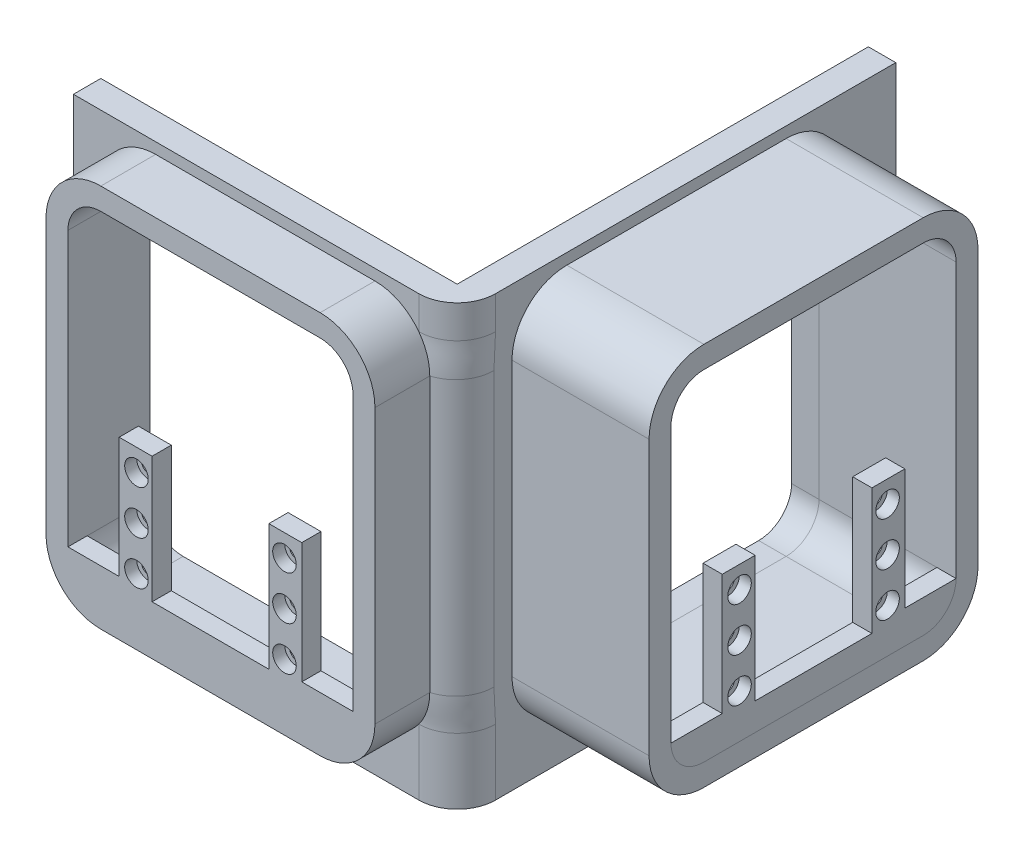
SolidWorks part; units mm, degrees
ref_plane "Front Plane" through (0, 0, 0) normal (0, 0, 1) x (1, 0, 0)
ref_plane "Top Plane" through (0, 0, 0) normal (0, 1, 0) x (1, 0, 0)
ref_plane "Right Plane" through (0, 0, 0) normal (1, 0, 0) x (0, 0, -1)
sketch "Sketch1" plane through (0, 0, 0) normal (0, 0, 1) x (1, 0, 0)
  line L1 (-20, -35) -> (20, -35)
  line L2 (-30, -25) -> (-30, 25)
  line L3 (-20, 35) -> (20, 35)
  line L4 (30, -25) -> (30, 25)
  line L5 (-30, -35) -> (30, 35) construction
  line L6 (-30, 35) -> (30, -35) construction
  arc A1 (20, 35) -> (30, 25) centre (20, 25) cw
  arc A2 (20, -35) -> (30, -25) centre (20, -25) ccw
  arc A3 (-20, -35) -> (-30, -25) centre (-20, -25) cw
  arc A4 (-30, 25) -> (-20, 35) centre (-20, 25) cw
  point P0 (0, 0)
  dimension "D1" = 60
  dimension "D3" = 10
  dimension "D2" = 70
extrude "Boss-Extrude1" add sketch "Sketch1" against normal blind 10
ref_plane "Plane1" through (60, 0, 0) normal (1, 0, 0) x (0, 0, -1)
ref_plane "Plane2" through (60, 0, 0) normal (1, 0, 0) x (0, 0, -1)
sketch "Sketch10" plane through (0, 0, -10) normal (0, 0, -1) x (-1, 0, 0)
  line L0 (0, -3) -> (0, 0) construction
  line L1 (-35, -43) -> (35, -43)
  line L2 (-35, -43) -> (-35, 37)
  line L3 (-35, 37) -> (35, 37)
  line L4 (35, -43) -> (35, 37)
  line L5 (-35, -43) -> (35, 37) construction
  line L6 (-35, 37) -> (35, -43) construction
  point P0 (0, -3)
  dimension "D3" = 3
  dimension "D1" = 80
  dimension "D2" = 70
extrude "Boss-Extrude6" add sketch "Sketch10" along normal blind 80
sketch "Sketch2" plane through (60, 0, 0) normal (1, 0, 0) x (0, 0, -1)
  line L2 (0, 0) -> (146.6861, 0) construction
  line L3 (50, 0) -> (50, 30) construction
  line L5 (10, 37) -> (10, -43) construction
  line L6 (90, 37) -> (90, -43) construction
  line L7 (30, -35) -> (70, -35)
  line L8 (20, -25) -> (20, 25)
  line L9 (30, 35) -> (70, 35)
  line L10 (80, -25) -> (80, 25)
  line L11 (20, -35) -> (80, 35) construction
  line L12 (20, 35) -> (80, -35) construction
  arc A1 (30, -35) -> (20, -25) centre (30, -25) cw
  arc A2 (70, -35) -> (80, -25) centre (70, -25) ccw
  arc A3 (70, 35) -> (80, 25) centre (70, 25) cw
  arc A4 (20, 25) -> (30, 35) centre (30, 25) cw
  dimension "D1" = 60
  dimension "D3" = 10
  dimension "D2" = 70
extrude "Boss-Extrude2" add sketch "Sketch2" against normal up to surface (25 mm away) separate body up to face at (35, -3, -50)
sketch "Sketch11" plane through (0, 37, 0) normal (0, 1, 0) x (1, 0, 0)
  line L1 (-35, 90) -> (30, 90)
  line L2 (-35, 90) -> (-35, 15)
  line L3 (-35, 15) -> (30, 15)
  line L4 (30, 90) -> (30, 15)
  dimension "D1" = 75
  dimension "D2" = 65
extrude "Cut-Extrude5" cut sketch "Sketch11" against normal through all
sketch "Sketch4" plane through (35, 0, 0) normal (-1, 0, 0) x (0, 0, 1)
  line L8 (-70, -31) -> (-30, -31)
  line L9 (-76, 25) -> (-76, -25)
  line L10 (-30, 31) -> (-70, 31)
  line L11 (-24, -25) -> (-24, 25)
  line L12 (-70, -31) -> (-30, -31)
  line L13 (-76, 25) -> (-76, -25)
  line L14 (-30, 31) -> (-70, 31)
  line L15 (-24, -25) -> (-24, 25)
  arc A10 (-76, -25) -> (-70, -31) centre (-70, -25) ccw
  arc A11 (-70, 31) -> (-76, 25) centre (-70, 25) ccw
  arc A12 (-24, 25) -> (-30, 31) centre (-30, 25) ccw
  arc A13 (-30, -31) -> (-24, -25) centre (-30, -25) ccw
  arc A14 (-76, -25) -> (-70, -31) centre (-70, -25) ccw
  arc A15 (-70, 31) -> (-76, 25) centre (-70, 25) ccw
  arc A16 (-24, 25) -> (-30, 31) centre (-30, 25) ccw
  arc A17 (-30, -31) -> (-24, -25) centre (-30, -25) ccw
  dimension "D1" = 4
extrude "Cut-Extrude2" cut sketch "Sketch4" against normal through all contours L12 A17 L15 A16 L14 A15 L13 A14 region at (35, 0, -50)
sketch "Sketch5" plane through (60, 0, 0) normal (1, 0, 0) x (0, 0, -1)
  line L0 (50, 0) -> (50, -31) construction
  line L1 (33.35, -3) -> (39.35, -3)
  line L2 (39.35, -3) -> (39.35, -26)
  line L3 (39.35, -26) -> (60.65, -26)
  line L4 (60.65, -26) -> (60.65, -3)
  line L5 (60.65, -3) -> (66.65, -3)
  line L6 (66.65, -3) -> (66.65, -25)
  line L8 (33.35, -3) -> (33.35, -25)
  line L10 (50, 0) -> (63.5, 0) construction
  line L11 (63.5, 0) -> (63.5, -7) construction
  line L12 (63.5, -7) -> (63.5, -15) construction
  line L13 (63.5, -15) -> (63.5, -23) construction
  line L14 (70, -31) -> (30, -31) construction
  line L15 (30, -31) -> (70, -31)
  line L16 (33.35, -25) -> (24, -25)
  line L17 (66.65, -25) -> (76, -25)
  circle A0 centre (50, 0) radius 11 construction
  arc A1 (24, -25) -> (30, -31) centre (30, -25) ccw construction
  circle A2 centre (63.5, -7) radius 1.25
  arc A3 (24, -25) -> (30, -31) centre (30, -25) ccw
  circle A5 centre (63.5, -15) radius 1.25
  circle A6 centre (63.5, -23) radius 1.25
  circle A7 centre (36.5, -7) radius 1.25
  circle A8 centre (36.5, -15) radius 1.25
  circle A9 centre (36.5, -23) radius 1.25
  arc A10 (70, -31) -> (76, -25) centre (70, -25) ccw
  point P8 (50, -26)
  point P14 (50, -31)
  dimension "D1" = 22
  dimension "D6" = 2.5
  dimension "D3" = 21.3
  dimension "D4" = 13.5
  dimension "D5" = 7
  dimension "D7" = 8
  dimension "D8" = 8
  dimension "D9" = 6
  dimension "D10" = 5
  dimension "D12" = 3
extrude "Boss-Extrude3" add sketch "Sketch5" against normal blind 3.5
sketch "Sketch13" plane through (35, 0, 0) normal (1, 0, 0) x (0, 0, -1)
  line L4 (24, 25) -> (24, -25)
  line L5 (30, -31) -> (70, -31)
  line L6 (76, -25) -> (76, 25)
  line L7 (70, 31) -> (30, 31)
  line L8 (24, 25) -> (24, -25)
  line L9 (30, -31) -> (70, -31)
  line L10 (76, -25) -> (76, 25)
  line L11 (70, 31) -> (30, 31)
  arc A6 (30, 31) -> (24, 25) centre (30, 25) ccw
  arc A7 (24, -25) -> (30, -31) centre (30, -25) ccw
  arc A8 (70, -31) -> (76, -25) centre (70, -25) ccw
  arc A9 (76, 25) -> (70, 31) centre (70, 25) ccw
  arc A10 (30, 31) -> (24, 25) centre (30, 25) ccw
  arc A11 (24, -25) -> (30, -31) centre (30, -25) ccw
  arc A12 (70, -31) -> (76, -25) centre (70, -25) ccw
  arc A13 (76, 25) -> (70, 31) centre (70, 25) ccw
  dimension "D1" = 0
extrude "Cut-Extrude6" cut sketch "Sketch13" against normal up to surface (5 mm away) up to face at (30, -3, -52.5)
sketch "Sketch14" plane through (0, 0, 0) normal (0, 0, 1) x (1, 0, 0)
  line L8 (20, 31) -> (-20, 31)
  line L9 (26, -25) -> (26, 25)
  line L10 (-20, -31) -> (20, -31)
  line L11 (-26, 25) -> (-26, -25)
  line L12 (20, 31) -> (-20, 31)
  line L13 (26, -25) -> (26, 25)
  line L14 (-20, -31) -> (20, -31)
  line L15 (-26, 25) -> (-26, -25)
  arc A10 (26, 25) -> (20, 31) centre (20, 25) ccw
  arc A11 (20, -31) -> (26, -25) centre (20, -25) ccw
  arc A12 (-26, -25) -> (-20, -31) centre (-20, -25) ccw
  arc A13 (-20, 31) -> (-26, 25) centre (-20, 25) ccw
  arc A14 (26, 25) -> (20, 31) centre (20, 25) ccw
  arc A15 (20, -31) -> (26, -25) centre (20, -25) ccw
  arc A16 (-26, -25) -> (-20, -31) centre (-20, -25) ccw
  arc A17 (-20, 31) -> (-26, 25) centre (-20, 25) ccw
  dimension "D1" = 4
extrude "Cut-Extrude7" cut sketch "Sketch14" against normal up to surface (15 mm away) up to face at (-2.5, -3, -15)
sketch "Sketch15" plane through (0, 0, 0) normal (0, 0, 1) x (1, 0, 0)
  line L0 (0, 0) -> (0, -17.9719) construction
  line L1 (-16.65, -3) -> (-10.65, -3)
  line L2 (-10.65, -3) -> (-10.65, -26)
  line L3 (-10.65, -26) -> (10.65, -26)
  line L4 (10.65, -26) -> (10.65, -3)
  line L5 (10.65, -3) -> (16.65, -3)
  line L6 (16.65, -3) -> (16.65, -25)
  line L8 (-16.65, -3) -> (-16.65, -25)
  line L10 (0, 0) -> (13.5, 0) construction
  line L11 (13.5, 0) -> (13.5, -7) construction
  line L12 (13.5, -7) -> (13.5, -15) construction
  line L13 (13.5, -15) -> (13.5, -23) construction
  line L14 (-20, -31) -> (20, -31) construction
  line L15 (-20, -31) -> (20, -31)
  line L16 (26, -25) -> (16.65, -25)
  line L17 (-26, -25) -> (-16.65, -25)
  circle A0 centre (0, 0) radius 11 construction
  circle A1 centre (13.5, -7) radius 1.25
  circle A3 centre (13.5, -15) radius 1.25
  circle A4 centre (13.5, -23) radius 1.25
  circle A5 centre (-13.5, -7) radius 1.25
  circle A6 centre (-13.5, -15) radius 1.25
  circle A7 centre (-13.5, -23) radius 1.25
  arc A9 (-26, -25) -> (-20, -31) centre (-20, -25) ccw
  arc A10 (26, -25) -> (20, -31) centre (20, -25) cw
  point P5 (0, -26)
  dimension "D1" = 22
  dimension "D5" = 2.5
  dimension "D2" = 21.3
  dimension "D3" = 13.5
  dimension "D4" = 7
  dimension "D6" = 8
  dimension "D7" = 8
  dimension "D8" = 6
  dimension "D9" = 5
  dimension "D10" = 3
extrude "Boss-Extrude7" add sketch "Sketch15" against normal blind 3.5
sketch "Sketch16" plane through (60, 0, 0) normal (1, 0, 0) x (0, 0, -1)
  circle A0 centre (63.5, -7) radius 2.15
  circle A1 centre (63.5, -15) radius 2.15
  circle A2 centre (63.5, -23) radius 2.15
  circle A3 centre (36.5, -23) radius 2.15
  circle A4 centre (36.5, -15) radius 2.15
  circle A5 centre (36.5, -7) radius 2.15
  dimension "D1" = 4.3
extrude "Cut-Extrude8" cut sketch "Sketch16" against normal blind 2.2
fillet "Fillet1" radius 7 1 edges at (35, -3, -10)
fillet "Fillet2" [suppressed] radius 10
sketch "Sketch17" plane through (0, 0, 0) normal (0, 0, 1) x (1, 0, 0)
  circle A0 centre (-13.5, -7) radius 2.15
  circle A1 centre (-13.5, -15) radius 2.15
  circle A2 centre (-13.5, -23) radius 2.15
  circle A3 centre (13.5, -7) radius 2.15
  circle A4 centre (13.5, -15) radius 2.15
  circle A5 centre (13.5, -23) radius 2.15
  dimension "D1" = 4.3
extrude "Cut-Extrude9" cut sketch "Sketch17" against normal blind 2.2
